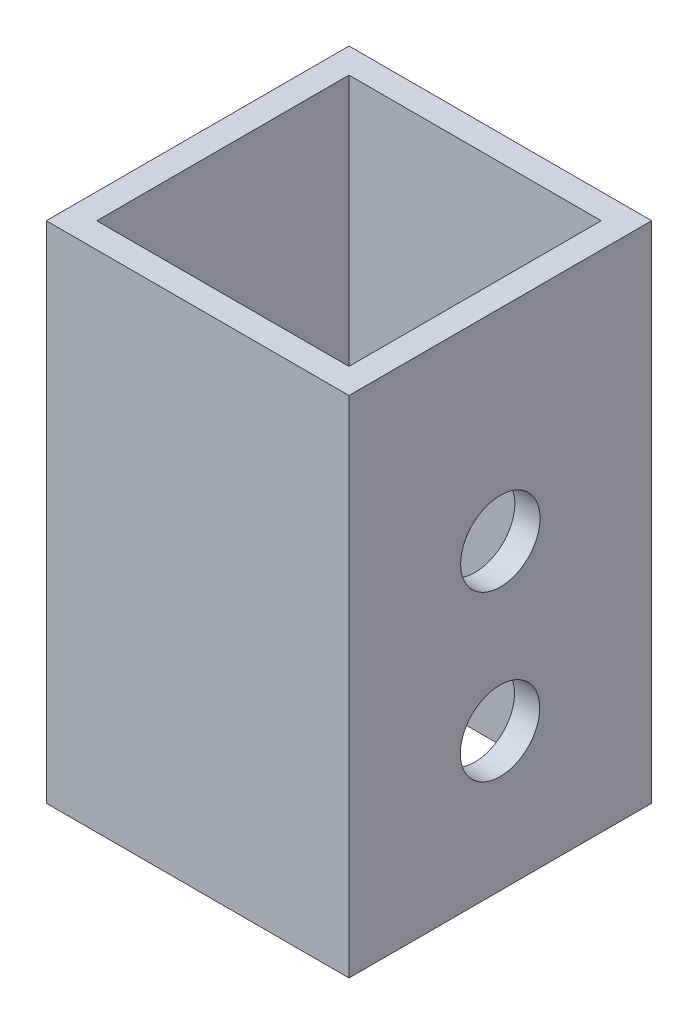
SolidWorks part; units mm, degrees
ref_plane "Front Plane" through (0, 0, 0) normal (0, 0, 1) x (1, 0, 0)
ref_plane "Top Plane" through (0, 0, 0) normal (0, 1, 0) x (1, 0, 0)
ref_plane "Right Plane" through (0, 0, 0) normal (1, 0, 0) x (0, 0, -1)
sketch "Sketch1" plane through (0, 0, 0) normal (0, 1, 0) x (1, 0, 0)
  line L1 (-38.1, -38.1) -> (38.1, -38.1)
  line L2 (-38.1, -38.1) -> (-38.1, 38.1)
  line L3 (-38.1, 38.1) -> (38.1, 38.1)
  line L4 (38.1, -38.1) -> (38.1, 38.1)
  line L5 (-38.1, -38.1) -> (38.1, 38.1) construction
  line L6 (-38.1, 38.1) -> (38.1, -38.1) construction
  line L7 (-31.75, -31.75) -> (31.75, -31.75)
  line L8 (-31.75, -31.75) -> (-31.75, 31.75)
  line L9 (-31.75, 31.75) -> (31.75, 31.75)
  line L10 (31.75, -31.75) -> (31.75, 31.75)
  line L11 (-31.75, -31.75) -> (31.75, 31.75) construction
  line L12 (-31.75, 31.75) -> (31.75, -31.75) construction
  point P0 (0, 0)
  point P6 (0, 0)
  dimension "D1" = 76.2
  dimension "D2" = 76.2
  dimension "D3" = 6.35
  dimension "D4" = 6.35
extrude "Boss-Extrude3" add sketch "Sketch1" along normal blind 127
sketch "Sketch5" plane through (-38.1, 0, 0) normal (-1, 0, 0) x (0, 0, 1)
  line L1 (-29.1299, 64.0935) -> (29.2901, 64.0935) construction
  line L2 (-29.1299, 64.0935) -> (-29.1299, 5.6735) construction
  line L3 (-29.1299, 5.6735) -> (29.2901, 5.6735) construction
  line L4 (29.2901, 64.0935) -> (29.2901, 5.6735) construction
  line L5 (-29.1299, 64.0935) -> (29.2901, 5.6735) construction
  line L6 (-29.1299, 5.6735) -> (29.2901, 64.0935) construction
  circle A0 centre (0.0801, 34.8835) radius 33.3375 construction
  circle A1 centre (-23.493, 58.4567) radius 2.4765
  circle A2 centre (23.6533, 58.4567) radius 2.4765
  circle A3 centre (23.6533, 11.3104) radius 2.4765
  circle A4 centre (-23.493, 11.3104) radius 2.4765
  circle A5 centre (0.0801, 34.8835) radius 10
  point P4 (0.0801, 34.8835)
  dimension "D3" = 66.675
  dimension "D4" = 4.953
  dimension "D5" = 4.953
  dimension "D6" = 4.953
  dimension "D7" = 4.953
  dimension "D8" = 20
  dimension "D1" = 58.42
  dimension "D2" = 58.42
sketch "Sketch6" plane through (-38.1, 0, 0) normal (-1, 0, 0) x (0, 0, 1)
  line L0 (0, 0) -> (0, 127) construction
  line L1 (-38.1, 0) -> (38.1, 0) construction
  line L2 (-38.1, 127) -> (38.1, 127) construction
  circle A0 centre (0, 76.2) radius 10
  dimension "D1" = 20
  dimension "D2" = 76.2
extrude "Cut-Extrude4" cut sketch "Sketch5" against normal up to next contours A1 | A4 | A3 | A2
extrude "Cut-Extrude5" cut sketch "Sketch5<3>" against normal through all contours A5
sketch "Sketch5<3>" plane through (-38.1, 0, 0) normal (-1, 0, 0) x (0, 0, 1) same geometry as "Sketch5"
sketch "Sketch8" plane through (31.75, 0, 0) normal (-1, 0, 0) x (0, 0, 1)
  line L1 (-6.8222, 99.4908) -> (18.5778, 99.4908)
  line L2 (-6.8222, 99.4908) -> (-6.8222, 74.0908)
  line L3 (-6.8222, 74.0908) -> (18.5778, 74.0908)
  line L4 (18.5778, 99.4908) -> (18.5778, 74.0908)
  line L5 (-6.8222, 99.4908) -> (18.5778, 74.0908) construction
  line L6 (-6.8222, 74.0908) -> (18.5778, 99.4908) construction
  point P4 (5.8778, 86.7908)
  dimension "D1" = 25.4
  dimension "D2" = 25.4
extrude "Cut-Extrude6" cut sketch "Sketch6" against normal through all
equation "\"wheelPitchD\"= 16mm"
equation "\"wheelClearanceD\"= 18mm"
equation "\"wormPitchD\"= 12mm"
equation "\"wormClearanceD\"= 14mm"
equation "\"ShaftD\"= 0.25in"
equation "\"MountingDistance\" = 14mm"
equation "\"HubDiameter\"= 12mm"
equation "\"HubWidth\"= 8mm"
equation "\"FaceWidth\"= 8mm"
equation "\"CentralPivotBearingD\"= 1.125in"
